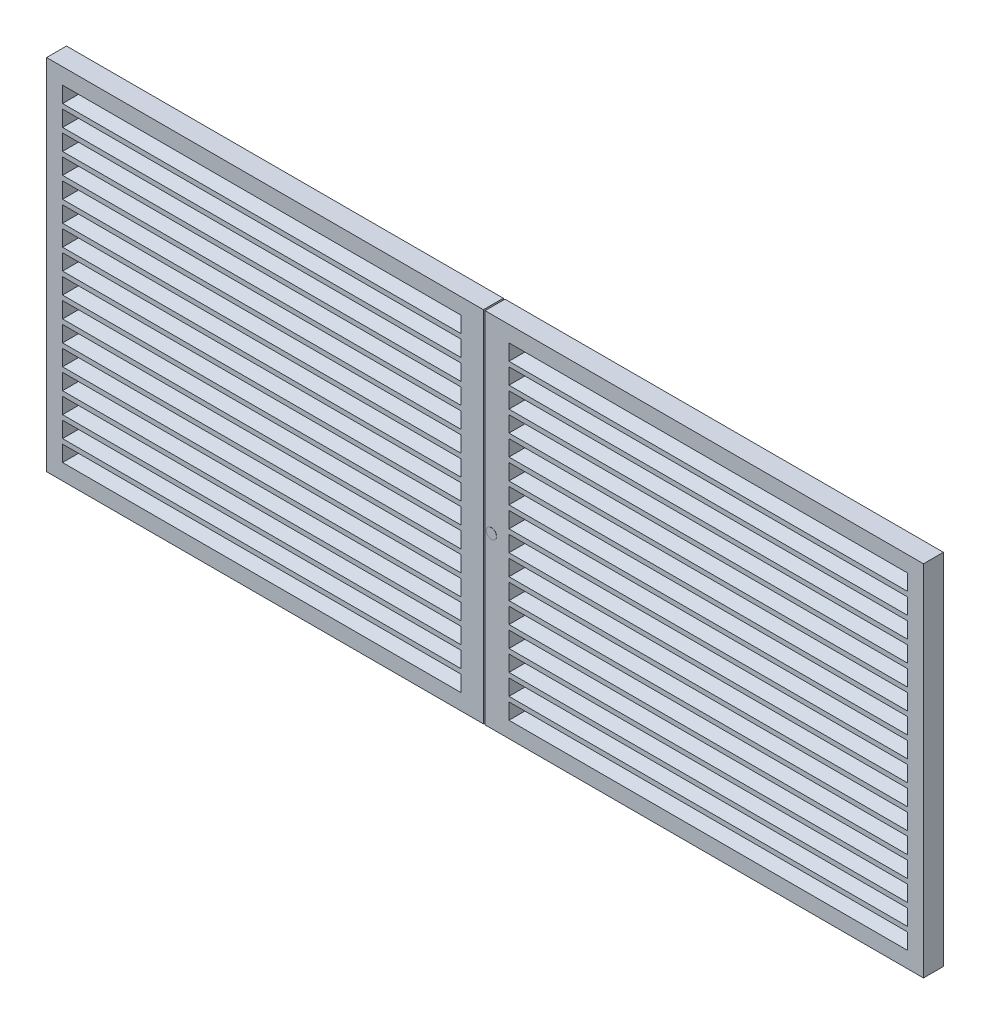
SolidWorks part; units mm, degrees
ref_plane "Alzado" through (0, 0, 0) normal (0, 0, 1) x (1, 0, 0)
ref_plane "Planta" through (0, 0, 0) normal (0, 1, 0) x (1, 0, 0)
ref_plane "Vista lateral" through (0, 0, 0) normal (1, 0, 0) x (0, 0, -1)
sketch "Croquis1" plane through (0, 0, 0) normal (0, 0, 1) x (1, 0, 0)
  line L1 (0, 0) -> (11000, 0)
  line L2 (0, 0) -> (0, 4500)
  line L3 (0, 4500) -> (11000, 4500)
  line L4 (11000, 0) -> (11000, 4500)
  dimension "D1" = 11000
  dimension "D2" = 4500
extrude "Saliente-Extruir1" add sketch "Croquis1" along normal blind 250
sketch "Croquis2" plane through (0, 0, 250) normal (0, 0, 1) x (1, 0, 0)
  line L0 (11000, 4500) -> (0, 4500) construction
  line L1 (200, 4300) -> (5200, 4300)
  line L2 (200, 4300) -> (200, 4100)
  line L3 (200, 4100) -> (5200, 4100)
  line L4 (5200, 4300) -> (5200, 4100)
  line L5 (0, 4500) -> (0, 0) construction
  line L6 (11000, 0) -> (11000, 4500) construction
  line L7 (10800, 4300) -> (5800, 4300)
  line L8 (10800, 4300) -> (10800, 4100)
  line L9 (10800, 4100) -> (5800, 4100)
  line L10 (5800, 4300) -> (5800, 4100)
  dimension "D1" = 200
  dimension "D2" = 200
  dimension "D3" = 200
  dimension "D4" = 200
  dimension "D5" = 5000
  dimension "D6" = 5000
extrude "Cortar-Extruir1" cut sketch "Croquis2" against normal blind 250 draft 20
pattern_linear "MatrizL1" count 16 spacing 260 along (0, -1, 0) of "Cortar-Extruir1"
sketch "Croquis3" plane through (0, 0, 250) normal (0, 0, 1) x (1, 0, 0)
  circle A0 centre (5580.8434, 2120) radius 64.1496
extrude "Saliente-Extruir2" add sketch "Croquis3" along normal blind 2
sketch "Croquis4" plane through (0, 0, 250) normal (0, 0, 1) x (1, 0, 0)
  line L0 (11000, 4500) -> (0, 4500) construction
  line L1 (5500, 4500) -> (5479.4917, 4500)
  line L2 (5500, 4500) -> (5500, 0)
  line L3 (5500, 0) -> (5479.4917, 0)
  line L4 (5479.4917, 4500) -> (5479.4917, 0)
  line L5 (0, 0) -> (11000, 0) construction
extrude "Cortar-Extruir2" cut sketch "Croquis4" against normal up to surface (250 mm away) up to face at (2700, 3940, 0)
